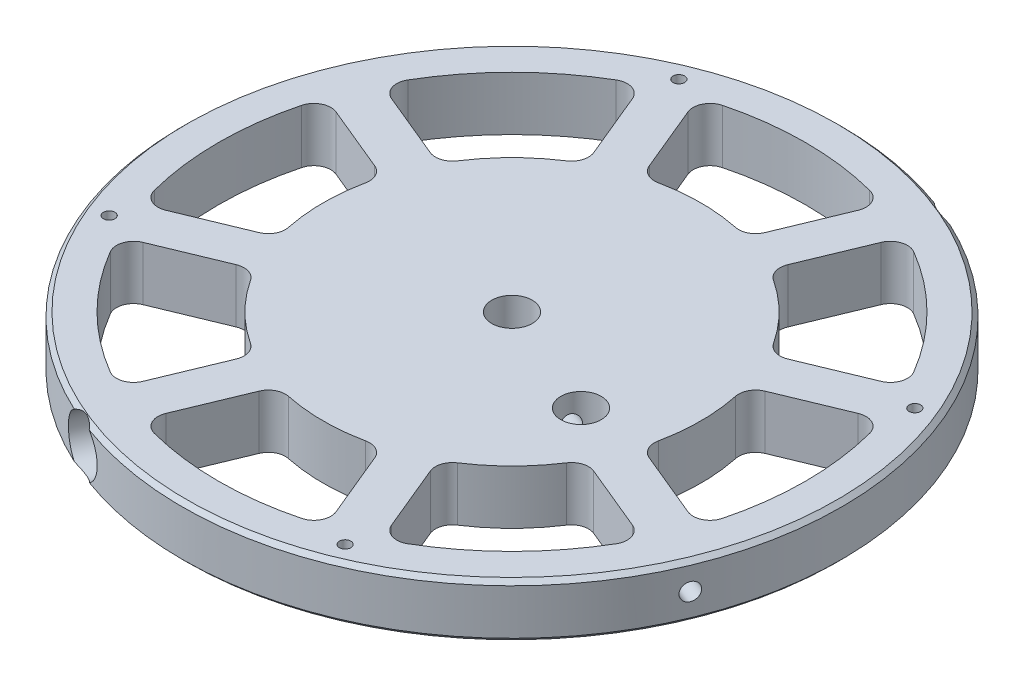
SolidWorks part; units mm, degrees
material "6061-T6 (SS)"
ref_plane "Front Plane" through (0, 0, 0) normal (0, 0, 1) x (1, 0, 0)
ref_plane "Top Plane" through (0, 0, 0) normal (0, 1, 0) x (1, 0, 0)
ref_plane "Right Plane" through (0, 0, 0) normal (1, 0, 0) x (0, 0, -1)
sketch "Sketch2" plane through (0, 0, 0) normal (1, 0, 0) x (0, 0, -1)
  line L0 (0, 0) -> (-77.55, 0)
  line L1 (-77.55, 0) -> (-77.55, 12.7)
  line L2 (-77.55, 12.7) -> (0, 12.7)
  line L5 (0, 12.7) -> (0, 0)
  dimension "D1" = 77.55
  dimension "D2" = 12.7
ref_axis "Axis1" through (0, -0.75, 0) along (0, 1, 0)
revolve "Revolve1" add sketch "Sketch2" angle 360 about axis through (0, -0.75, 0) along (0, 1, 0)
hole_wizard "#6-32 Tapped Hole2" positions "Sketch6" profile "Sketch7" tap size "#6-32" standard "ANSI Inch" end condition through all
sketch "Sketch6" plane through (0, 12.7, 0) normal (0, 1, 0) x (1, 0, 0)
  line L0 (0, 0) -> (-53.438, 129.0108) construction
  line L2 (0, 0) -> (0, 109.0908) construction
  point P0 (-27.7637, 67.0275)
  dimension "D1" = 22.5
  dimension "D2" = 72.55
sketch "Sketch7" plane through (-27.7637, 12.7, -67.0275) normal (1, 0, 0) x (0, 0, 1)
  line L0 (0, 0) -> (0, 12.7)
  line L1 (0, 12.7) -> (1.3525, 12.7)
  line L2 (1.3525, 12.7) -> (1.3525, 0)
  line L5 (1.3525, 0) -> (0, 0)
  line L11 (0, -6.35) -> (0, 107.95) construction
  dimension "Thread Major Dia." = 2.7051
  dimension "Thru Tap Drill Depth" = 12.7
pattern_circular "CirPattern3" count 4 over 360 about axis through (0, -0.75, 0) along (0, 1, 0) of "#6-32 Tapped Hole2"
sketch "Sketch8" plane through (0, 12.7, 0) normal (0, 1, 0) x (1, 0, 0)
  line L4 (0, 0) -> (0, 93.9995) construction
  line L5 (0, 0) -> (113.8372, 0) construction
  line L6 (-12.2829, 42.7192) -> (-21.7355, 65.5398)
  line L7 (12.2829, 42.7192) -> (21.7355, 65.5398)
  line L8 (0, 0) -> (-27.7637, 67.0275) construction
  arc A0 (-12.2829, 42.7192) -> (12.2829, 42.7192) centre (0, 0) cw
  arc A1 (-21.7355, 65.5398) -> (21.7355, 65.5398) centre (0, 0) cw
  circle A2 centre (0, 0) radius 77.55 construction
  dimension "D1" = 44.45
  dimension "D2" = 8.5
  dimension "D3" = 5
extrude "Cut-Extrude1" cut sketch "Sketch8" against normal through all
fillet "Fillet1" radius 4 4 edges at (12.2829, 6.35, -42.7192) (21.7355, 6.35, -65.5398) (-12.2829, 6.35, -42.7192) (-21.7355, 6.35, -65.5398)
pattern_circular "CirPattern4" count 8 over 360 about axis through (0, -0.75, 0) along (0, 1, 0) of "Cut-Extrude1", "Fillet1"
chamfer "Chamfer1" distance 1 angle 45 2 edges at (0, 0, -77.55) (0, 12.7, -77.55)
ref_plane "Plane1" through (0, 0, 0) normal (0.9239, 0, 0.3827) x (0, 1, 0)
hole_wizard "#20 (0.161) Diameter Hole1" positions "Sketch16" profile "Sketch15" hole size "#20" standard "ANSI Inch" end condition through all
sketch "Sketch16" plane through (0, 0, 0) normal (0.9239, 0, 0.3827) x (0, 1, 0)
  point P0 (6.35, 0)
  dimension "D1" = 6.35
sketch "Sketch15" plane through (0, 6.35, 0) normal (0, 1, 0) x (-0.3827, 0, 0.9239)
  line L0 (0, 0) -> (0, 101.324)
  line L1 (0, 101.324) -> (2.0447, 101.324)
  line L2 (2.0447, 101.324) -> (2.0447, 0)
  line L5 (2.0447, 0) -> (0, 0)
  line L11 (0, -6.35) -> (0, 107.95) construction
  dimension "Thru Hole Dia." = 4.0894
  dimension "Thru Hole Depth" = 101.324
ref_plane "Plane2" through (29.6771, 0, -71.6469) normal (0.3827, 0, -0.9239) x (-0.9239, 0, -0.3827)
sketch "Sketch19" plane through (29.6771, 0, -71.6469) normal (0.3827, 0, -0.9239) x (-0.9239, 0, -0.3827)
  line L0 (-76.55, 0) -> (76.55, 0) construction
  line L2 (0, -0.75) -> (0, 15.75) construction
  circle A0 centre (0, 6.35) radius 5.5625 construction
  circle A1 centre (0, 6.35) radius 6.25
  dimension "D1" = 12.5
  dimension "D2" = 6.35
extrude "Cut-Extrude3" cut sketch "Sketch19" against normal blind 5
pattern_circular "CirPattern5" count 2 over 360 about axis through (0, -0.75, 0) along (0, 1, 0) of "Cut-Extrude3"
hole_wizard "#10-24 Tapped Hole1" positions "Sketch20" profile "Sketch21" tap size "#10-24" standard "ANSI Inch"
sketch "Sketch20" plane through (-27.7637, 0, 67.0275) normal (-0.3827, 0, 0.9239) x (0.9239, 0, 0.3827)
  circle A0 centre (0, 6.35) radius 6.25
  circle A1 centre (0, 6.35) radius 6.25 construction
  point P0 (0, 6.35)
sketch "Sketch21" plane through (-27.7637, 6.35, 67.0275) normal (0, 1, 0) x (0.9239, 0, 0.3827)
  line L0 (0, 0) -> (0, 51.9408)
  line L1 (0, 51.9408) -> (1.8986, 50.8)
  line L2 (1.8986, 50.8) -> (1.8986, 0)
  line L5 (1.8986, 0) -> (0, 0)
  line L10 (0, 51.9408) -> (-1.8986, 50.8) construction
  line L11 (0, -6.35) -> (0, 107.95) construction
  dimension "Tap Drill Dia." = 3.7973
  dimension "Tap Drill Depth" = 50.8
  dimension "Drill Angle" = 118
pattern_circular "CirPattern6" count 2 over 360 about axis through (0, -0.75, 0) along (0, 1, 0) of "#10-24 Tapped Hole1"
sketch "Sketch22" plane through (0, 12.7, 0) normal (0, 1, 0) x (1, 0, 0)
  circle A0 centre (0, 0) radius 4.765
  dimension "D1" = 9.53
extrude "Cut-Extrude4" cut sketch "Sketch22" against normal blind 12.8
pattern_linear "LPattern1" count 2 spacing 30 along (0.9239, 0, 0.3827) of "Cut-Extrude4"
equation "\"TubeDiameter\" = 6.500in"
equation "\"D1@Sketch2\"=(\"TubeDiameter\"/2)-5mm"
equation "\"D2@Sketch6\"=\"TubeDiameter\"/2-10mm"
